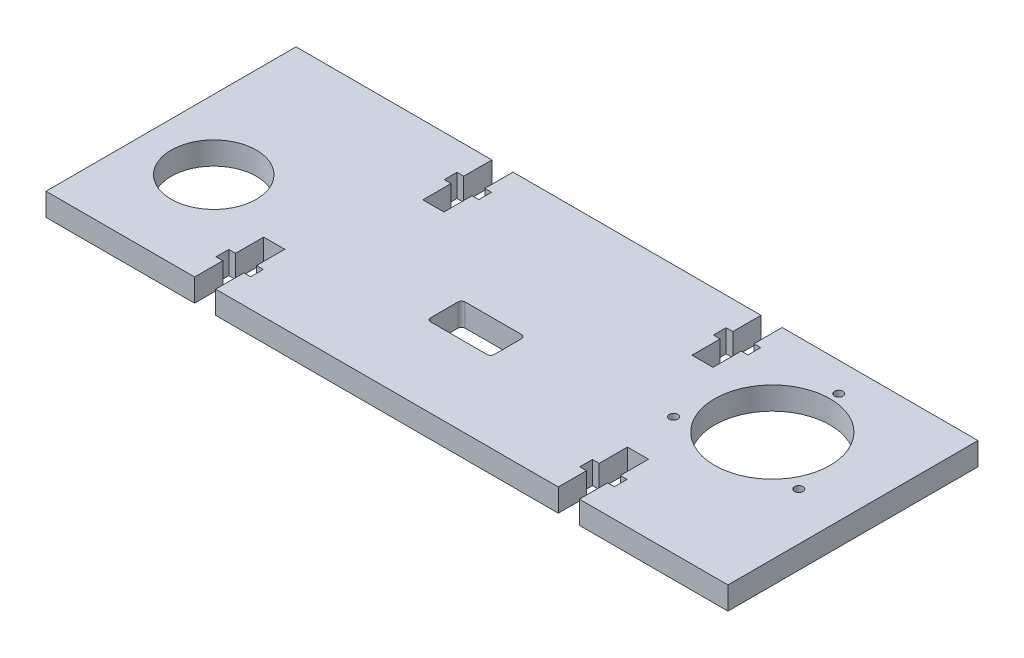
SolidWorks part; units mm, degrees
material "Acrylic (Medium-high impact)"
ref_plane "Front Plane" through (0, 0, 0) normal (0, 0, 1) x (1, 0, 0)
ref_plane "Top Plane" through (0, 0, 0) normal (0, 1, 0) x (1, 0, 0)
ref_plane "Right Plane" through (0, 0, 0) normal (1, 0, 0) x (0, 0, -1)
sketch "Sketch1" plane through (0, 0, 0) normal (0, 1, 0) x (1, 0, 0)
  line L1 (-47.625, -17.4625) -> (47.625, -17.4625)
  line L2 (-47.625, -17.4625) -> (-47.625, 17.4625)
  line L3 (-47.625, 17.4625) -> (47.625, 17.4625)
  line L4 (47.625, -17.4625) -> (47.625, 17.4625)
  line L5 (-47.625, -17.4625) -> (47.625, 17.4625) construction
  line L6 (-47.625, 17.4625) -> (47.625, -17.4625) construction
  point P0 (0, 0)
  dimension "D1" = 95.25
  dimension "D2" = 34.925
extrude "Boss-Extrude1" add sketch "Sketch1" along normal blind 3.175
hole_wizard "Tap Drill for #0-80 Tap1" positions "Sketch2" profile "Sketch3" hole size "#0-80" standard "ANSI Inch" end condition through all
sketch "Sketch2" plane through (0, 3.175, 0) normal (0, 1, 0) x (1, 0, 0)
  point P0 (40.9766, -0.9208)
  point P3 (23.4886, -0.9208)
  point P6 (32.2326, 13.4048)
sketch "Sketch3" plane through (40.9766, 3.175, 0.9208) normal (1, 0, 0) x (0, 0, 1)
  line L0 (0, 0) -> (0, 3.175)
  line L1 (0, 3.175) -> (0.5956, 3.175)
  line L2 (0.5956, 3.175) -> (0.5956, 0)
  line L5 (0.5956, 0) -> (0, 0)
  line L11 (0, -6.35) -> (0, 107.95) construction
  dimension "Thru Hole Dia." = 1.1913
  dimension "Thru Hole Depth" = 3.175
hole_wizard "7/16 Clearance Hole1" positions "Sketch4" profile "Sketch5" hole size "7/16" standard "ANSI Inch" end condition through all
sketch "Sketch4" plane through (0, 3.175, 0) normal (0, 1, 0) x (1, 0, 0)
  point P0 (-37.9095, -3.7465)
sketch "Sketch5" plane through (-37.9095, 3.175, 3.7465) normal (1, 0, 0) x (0, 0, 1)
  line L0 (0, 0) -> (0, 3.175)
  line L1 (0, 3.175) -> (5.9525, 3.175)
  line L2 (5.9525, 3.175) -> (5.9525, 0)
  line L5 (5.9525, 0) -> (0, 0)
  line L11 (0, -6.35) -> (0, 107.95) construction
  dimension "Thru Hole Dia." = 11.905
  dimension "Thru Hole Depth" = 3.175
sketch "Sketch6" plane through (0, 3.175, 0) normal (0, 1, 0) x (1, 0, 0)
  line L1 (3.429, -6.4135) -> (-5.461, -6.4135)
  line L2 (3.429, -6.4135) -> (3.429, -1.5875)
  line L3 (3.429, -1.5875) -> (-5.461, -1.5875)
  line L4 (-5.461, -6.4135) -> (-5.461, -1.5875)
extrude "Cut-Extrude1" cut sketch "Sketch6" against normal through all
sketch "Sketch7" plane through (0, 3.175, 0) normal (0, 1, 0) x (1, 0, 0)
  line L0 (47.625, -17.4625) -> (47.625, 17.4625) construction
  line L1 (47.625, -12.5857) -> (42.164, -12.5857)
  line L2 (47.625, -12.5857) -> (47.625, -9.6393)
  line L3 (47.625, -9.6393) -> (42.164, -9.6393)
  line L4 (34.925, -12.5857) -> (34.925, -9.6393)
  line L5 (47.625, -12.5857) -> (34.925, -9.6393) construction
  line L6 (47.625, -11.1125) -> (34.925, -11.1125) construction
  line L7 (-47.625, -17.4625) -> (47.625, -17.4625) construction
  line L8 (47.625, 9.6393) -> (42.164, 9.6393)
  line L9 (42.164, -8.6995) -> (40.386, -8.6995)
  line L10 (42.164, -8.6995) -> (42.164, -9.6393)
  line L11 (42.164, -13.5255) -> (40.386, -13.5255)
  line L12 (40.386, -8.6995) -> (40.386, -9.6393)
  line L13 (42.164, -8.6995) -> (40.386, -13.5255) construction
  line L14 (42.164, -13.5255) -> (40.386, -8.6995) construction
  line L15 (42.164, -12.5857) -> (42.164, -13.5255)
  line L16 (40.386, -9.6393) -> (34.925, -9.6393)
  line L17 (40.386, -12.5857) -> (40.386, -13.5255)
  line L18 (40.386, -12.5857) -> (34.925, -12.5857)
  line L19 (47.625, 9.6393) -> (47.625, 12.5857)
  line L20 (47.625, 12.5857) -> (42.164, 12.5857)
  line L21 (34.925, 9.6393) -> (34.925, 12.5857)
  line L22 (42.164, 13.5255) -> (40.386, 13.5255)
  line L23 (42.164, 13.5255) -> (42.164, 12.5857)
  line L24 (42.164, 8.6995) -> (40.386, 8.6995)
  line L25 (40.386, 13.5255) -> (40.386, 12.5857)
  line L26 (42.164, 9.6393) -> (42.164, 8.6995)
  line L27 (40.386, 12.5857) -> (34.925, 12.5857)
  line L28 (40.386, 9.6393) -> (40.386, 8.6995)
  line L29 (40.386, 9.6393) -> (34.925, 9.6393)
  line L30 (47.625, 9.6393) -> (34.925, 12.5857) construction
  line L31 (47.625, 11.1125) -> (34.925, 11.1125) construction
  line L32 (42.164, 13.5255) -> (40.386, 8.6995) construction
  line L33 (42.164, 8.6995) -> (40.386, 13.5255) construction
  line L34 (0, 0) -> (0, 17.4625) construction
  line L35 (47.625, 17.4625) -> (-47.625, 17.4625) construction
  line L36 (-42.164, 8.6995) -> (-40.386, 13.5255) construction
  line L37 (-42.164, 13.5255) -> (-40.386, 8.6995) construction
  line L38 (-47.625, 11.1125) -> (-34.925, 11.1125) construction
  line L39 (-47.625, 9.6393) -> (-34.925, 12.5857) construction
  line L40 (-42.164, -13.5255) -> (-40.386, -8.6995) construction
  line L41 (-42.164, -8.6995) -> (-40.386, -13.5255) construction
  line L42 (-47.625, -11.1125) -> (-34.925, -11.1125) construction
  line L43 (-47.625, -12.5857) -> (-34.925, -9.6393) construction
  line L44 (-40.386, 9.6393) -> (-34.925, 9.6393)
  line L45 (-40.386, 9.6393) -> (-40.386, 8.6995)
  line L46 (-40.386, 12.5857) -> (-34.925, 12.5857)
  line L47 (-42.164, 9.6393) -> (-42.164, 8.6995)
  line L48 (-40.386, 13.5255) -> (-40.386, 12.5857)
  line L49 (-42.164, 8.6995) -> (-40.386, 8.6995)
  line L50 (-42.164, 13.5255) -> (-42.164, 12.5857)
  line L51 (-42.164, 13.5255) -> (-40.386, 13.5255)
  line L52 (-34.925, 9.6393) -> (-34.925, 12.5857)
  line L53 (-47.625, 12.5857) -> (-42.164, 12.5857)
  line L54 (-47.625, 9.6393) -> (-47.625, 12.5857)
  line L55 (-40.386, -12.5857) -> (-34.925, -12.5857)
  line L56 (-40.386, -12.5857) -> (-40.386, -13.5255)
  line L57 (-40.386, -9.6393) -> (-34.925, -9.6393)
  line L58 (-42.164, -12.5857) -> (-42.164, -13.5255)
  line L59 (-40.386, -8.6995) -> (-40.386, -9.6393)
  line L60 (-42.164, -13.5255) -> (-40.386, -13.5255)
  line L61 (-42.164, -8.6995) -> (-42.164, -9.6393)
  line L62 (-42.164, -8.6995) -> (-40.386, -8.6995)
  line L63 (-47.625, 9.6393) -> (-42.164, 9.6393)
  line L64 (-34.925, -12.5857) -> (-34.925, -9.6393)
  line L65 (-47.625, -9.6393) -> (-42.164, -9.6393)
  line L66 (-47.625, -12.5857) -> (-47.625, -9.6393)
  line L67 (-47.625, -12.5857) -> (-42.164, -12.5857)
  point P10 (41.275, -11.1125)
  point P26 (41.275, 11.1125)
  point P67 (-41.275, 11.1125)
  point P68 (-41.275, -11.1125)
  dimension "D1" = 6.35
  dimension "D2" = 2.9464
  dimension "D3" = 12.7
  dimension "D4" = 1.778
  dimension "D5" = 4.826
  dimension "D6" = 2
extrude "Cut-Extrude2" [suppressed] cut sketch "Sketch7" against normal through all
sketch "Sketch8" plane through (0, 3.175, 0) normal (0, 1, 0) x (1, 0, 0)
  line L0 (-47.625, -17.4625) -> (47.625, -17.4625) construction
  line L1 (23.9268, -17.4625) -> (26.8732, -17.4625)
  line L2 (23.9268, -17.4625) -> (23.9268, -13.5255)
  line L3 (23.9268, -7.8105) -> (26.8732, -7.8105)
  line L4 (26.8732, -17.4625) -> (26.8732, -13.5255)
  line L5 (25.4, -17.4625) -> (25.4, -7.8105) construction
  line L6 (23.9268, -13.5255) -> (22.987, -13.5255)
  line L7 (27.813, -11.7475) -> (26.8732, -11.7475)
  line L8 (27.813, -11.7475) -> (27.813, -13.5255)
  line L9 (27.813, -13.5255) -> (26.8732, -13.5255)
  line L10 (22.987, -11.7475) -> (22.987, -13.5255)
  line L11 (27.813, -11.7475) -> (22.987, -13.5255) construction
  line L12 (27.813, -13.5255) -> (22.987, -11.7475) construction
  line L13 (26.8732, -11.7475) -> (26.8732, -7.8105)
  line L14 (23.9268, -11.7475) -> (22.987, -11.7475)
  line L15 (23.9268, -11.7475) -> (23.9268, -7.8105)
  line L16 (-26.8732, -17.4625) -> (-23.9268, -17.4625)
  line L17 (-26.8732, -17.4625) -> (-26.8732, -13.5255)
  line L18 (-26.8732, -7.8105) -> (-23.9268, -7.8105)
  line L19 (-23.9268, -17.4625) -> (-23.9268, -13.5255)
  line L20 (-26.8732, -13.5255) -> (-27.813, -13.5255)
  line L21 (-22.987, -11.7475) -> (-23.9268, -11.7475)
  line L22 (-22.987, -11.7475) -> (-22.987, -13.5255)
  line L23 (-22.987, -13.5255) -> (-23.9268, -13.5255)
  line L24 (-27.813, -11.7475) -> (-27.813, -13.5255)
  line L25 (-23.9268, -11.7475) -> (-23.9268, -7.8105)
  line L26 (-26.8732, -11.7475) -> (-27.813, -11.7475)
  line L27 (-26.8732, -11.7475) -> (-26.8732, -7.8105)
  line L28 (-25.4, -17.4625) -> (-25.4, -7.8105) construction
  line L29 (-22.987, -11.7475) -> (-27.813, -13.5255) construction
  line L30 (-22.987, -13.5255) -> (-27.813, -11.7475) construction
  line L31 (0, 0) -> (-7.905, 0) construction
  line L32 (-22.987, 13.5255) -> (-27.813, 11.7475) construction
  line L33 (-22.987, 11.7475) -> (-27.813, 13.5255) construction
  line L34 (-25.4, 17.4625) -> (-25.4, 7.8105) construction
  line L35 (27.813, 13.5255) -> (22.987, 11.7475) construction
  line L36 (27.813, 11.7475) -> (22.987, 13.5255) construction
  line L37 (25.4, 17.4625) -> (25.4, 7.8105) construction
  line L38 (-26.8732, 11.7475) -> (-26.8732, 7.8105) construction
  line L39 (-26.8732, 11.7475) -> (-27.813, 11.7475) construction
  line L40 (-23.9268, 11.7475) -> (-23.9268, 7.8105) construction
  line L41 (-27.813, 11.7475) -> (-27.813, 13.5255) construction
  line L42 (-22.987, 13.5255) -> (-23.9268, 13.5255) construction
  line L43 (-22.987, 11.7475) -> (-22.987, 13.5255) construction
  line L44 (-22.987, 11.7475) -> (-23.9268, 11.7475) construction
  line L45 (-26.8732, 13.5255) -> (-27.813, 13.5255) construction
  line L46 (-23.9268, 17.4625) -> (-23.9268, 13.5255) construction
  line L47 (-26.8732, 7.8105) -> (-23.9268, 7.8105) construction
  line L48 (-26.8732, 17.4625) -> (-26.8732, 13.5255) construction
  line L49 (-26.8732, 17.4625) -> (-23.9268, 17.4625) construction
  line L50 (23.9268, 11.7475) -> (23.9268, 7.8105) construction
  line L51 (23.9268, 11.7475) -> (22.987, 11.7475) construction
  line L52 (26.8732, 11.7475) -> (26.8732, 7.8105) construction
  line L53 (22.987, 11.7475) -> (22.987, 13.5255) construction
  line L54 (27.813, 13.5255) -> (26.8732, 13.5255) construction
  line L55 (27.813, 11.7475) -> (27.813, 13.5255) construction
  line L56 (27.813, 11.7475) -> (26.8732, 11.7475) construction
  line L57 (23.9268, 13.5255) -> (22.987, 13.5255) construction
  line L58 (26.8732, 17.4625) -> (26.8732, 13.5255) construction
  line L59 (23.9268, 7.8105) -> (26.8732, 7.8105) construction
  line L60 (23.9268, 17.4625) -> (23.9268, 13.5255) construction
  line L61 (23.9268, 17.4625) -> (26.8732, 17.4625) construction
  line L63 (17.3228, 11.7475) -> (17.3228, 7.8105)
  line L64 (17.3228, 11.7475) -> (16.383, 11.7475)
  line L65 (20.2692, 11.7475) -> (20.2692, 7.8105)
  line L66 (16.383, 11.7475) -> (16.383, 13.5255)
  line L67 (21.209, 13.5255) -> (20.2692, 13.5255)
  line L68 (21.209, 11.7475) -> (21.209, 13.5255)
  line L69 (21.209, 11.7475) -> (20.2692, 11.7475)
  line L70 (17.3228, 13.5255) -> (16.383, 13.5255)
  line L71 (20.2692, 17.4625) -> (20.2692, 13.5255)
  line L72 (17.3228, 7.8105) -> (20.2692, 7.8105)
  line L73 (17.3228, 17.4625) -> (17.3228, 13.5255)
  line L74 (17.3228, 17.4625) -> (20.2692, 17.4625)
  line L75 (21.209, 13.5255) -> (16.383, 11.7475) construction
  line L76 (21.209, 11.7475) -> (16.383, 13.5255) construction
  line L77 (18.796, 17.4625) -> (18.796, 7.8105) construction
  line L78 (-20.2692, 11.7475) -> (-20.2692, 7.8105)
  line L79 (-20.2692, 11.7475) -> (-21.209, 11.7475)
  line L80 (-17.3228, 11.7475) -> (-17.3228, 7.8105)
  line L81 (-21.209, 11.7475) -> (-21.209, 13.5255)
  line L82 (-16.383, 13.5255) -> (-17.3228, 13.5255)
  line L83 (-16.383, 11.7475) -> (-16.383, 13.5255)
  line L84 (-16.383, 11.7475) -> (-17.3228, 11.7475)
  line L85 (-20.2692, 13.5255) -> (-21.209, 13.5255)
  line L86 (-17.3228, 17.4625) -> (-17.3228, 13.5255)
  line L87 (-20.2692, 7.8105) -> (-17.3228, 7.8105)
  line L88 (-20.2692, 17.4625) -> (-20.2692, 13.5255)
  line L89 (-20.2692, 17.4625) -> (-17.3228, 17.4625)
  line L90 (-16.383, 13.5255) -> (-21.209, 11.7475) construction
  line L91 (-16.383, 11.7475) -> (-21.209, 13.5255) construction
  line L92 (-18.796, 17.4625) -> (-18.796, 7.8105) construction
  point P8 (25.4, -12.6365)
  point P25 (-25.4, -12.6365)
  point P63 (-25.4, 12.6365)
  point P64 (25.4, 12.6365)
  point P80 (18.796, 12.6365)
  point P95 (-18.796, 12.6365)
  dimension "D1" = 25.4
  dimension "D2" = 9.652
  dimension "D3" = 1.778
  dimension "D4" = 4.826
  dimension "D5" = 2.9464
  dimension "D6" = 2
  dimension "D7" = 2
  dimension "D8" = 2
extrude "Cut-Extrude3" cut sketch "Sketch8" against normal through all
sketch "Sketch9" plane through (0, 3.175, 0) normal (0, 1, 0) x (1, 0, 0)
  circle A0 centre (32.2326, 4.1275) radius 8.0645
  dimension "D1" = 16.129
extrude "Cut-Extrude4" cut sketch "Sketch9" against normal through all
fillet "Fillet1" radius 0.508 4 edges at (3.429, 1.5875, 1.5875) (-5.461, 1.5875, 1.5875) (-5.461, 1.5875, 6.4135) (3.429, 1.5875, 6.4135)
equation "\"#4D\"= .116'slot for adding a #4 screw"
equation "\"D5@Sketch8\"=\"#4D\""
equation "\"#4H\"= .38'slot heigth for adding a #4 screw with 1/2\" length"
equation "\"mat\"= 1 / 8'thickness of material"
equation "\"D2@Sketch8\"=\"#4H\""
equation "\"D1@Boss-Extrude1\"=\"mat\""
